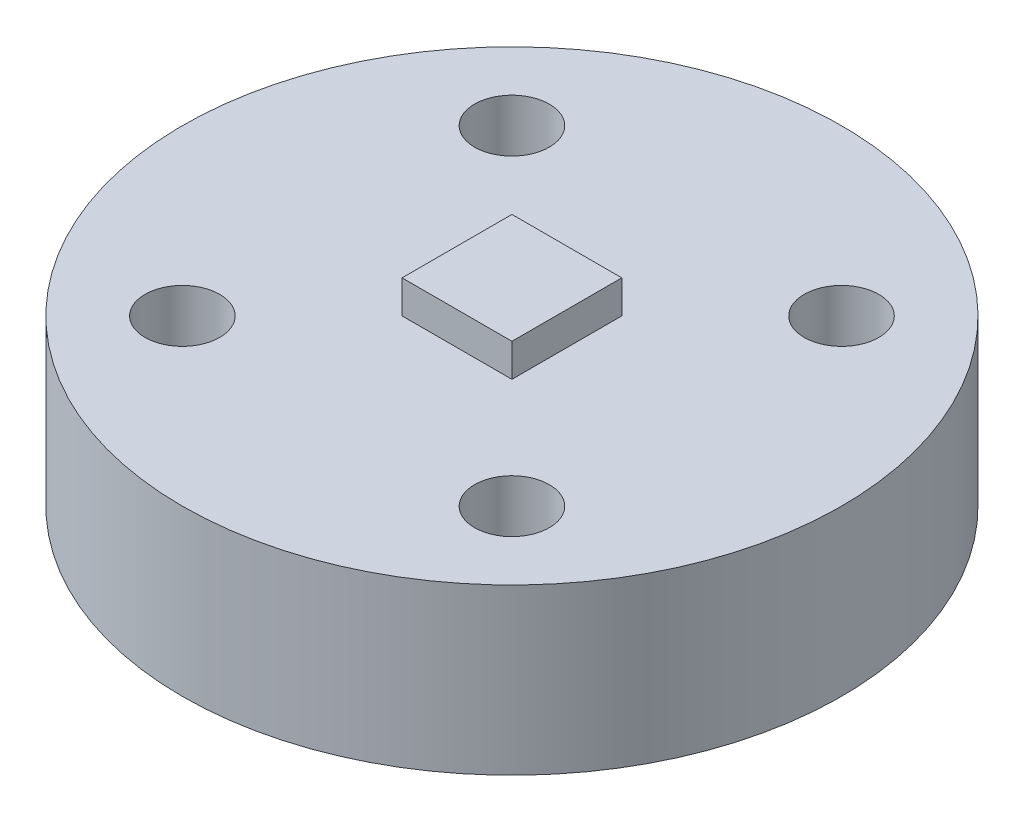
SolidWorks part; units mm, degrees
ref_plane "Front Plane" through (0, 0, 0) normal (0, 0, 1) x (1, 0, 0)
ref_plane "Top Plane" through (0, 0, 0) normal (0, 1, 0) x (1, 0, 0)
ref_plane "Right Plane" through (0, 0, 0) normal (1, 0, 0) x (0, 0, -1)
sketch "Sketch1" plane through (0, 0, 0) normal (0, 1, 0) x (1, 0, 0)
  circle A0 centre (0, 0) radius 30
  dimension "D1" = 60
extrude "Boss-Extrude1" add sketch "Sketch1" along normal blind 15
sketch "Sketch2" plane through (0, 15, 0) normal (0, 1, 0) x (1, 0, 0)
  line L1 (-5, -5) -> (5, -5)
  line L2 (-5, -5) -> (-5, 5)
  line L3 (-5, 5) -> (5, 5)
  line L4 (5, -5) -> (5, 5)
  line L5 (-5, -5) -> (5, 5) construction
  line L6 (-5, 5) -> (5, -5) construction
  point P0 (0, 0)
  dimension "D1" = 10
  dimension "D2" = 10
extrude "Boss-Extrude2" add sketch "Sketch2" along normal blind 3
sketch "Sketch3" plane through (0, 0, 0) normal (0, -1, 0) x (1, 0, 0)
  line L1 (5, 5) -> (-5, 5)
  line L2 (5, 5) -> (5, -5)
  line L3 (5, -5) -> (-5, -5)
  line L4 (-5, 5) -> (-5, -5)
  line L5 (5, 5) -> (-5, -5) construction
  line L6 (5, -5) -> (-5, 5) construction
  point P0 (0, 0)
  dimension "D1" = 10
  dimension "D2" = 10
extrude "Cut-Extrude1" cut sketch "Sketch3" against normal blind 3
sketch "Sketch6" plane through (0, 15, 0) normal (0, 1, 0) x (1, 0, 0)
  line L1 (15, 15) -> (-15, 15)
  line L2 (15, 15) -> (15, -15)
  line L3 (15, -15) -> (-15, -15)
  line L4 (-15, 15) -> (-15, -15)
  line L5 (15, 15) -> (-15, -15) construction
  line L6 (15, -15) -> (-15, 15) construction
  circle A0 centre (-15, -15) radius 3.4
  circle A1 centre (15, -15) radius 3.4
  circle A2 centre (15, 15) radius 3.4
  circle A3 centre (-15, 15) radius 3.4
  point P0 (0, 0)
  dimension "D3" = 6.8
  dimension "D4" = 6.8
  dimension "D5" = 6.8
  dimension "D6" = 6.8
  dimension "D1" = 30
  dimension "D2" = 30
extrude "Cut-Extrude3" cut sketch "Sketch6" against normal blind 10 contours A0 | A3 | A2 | A1
